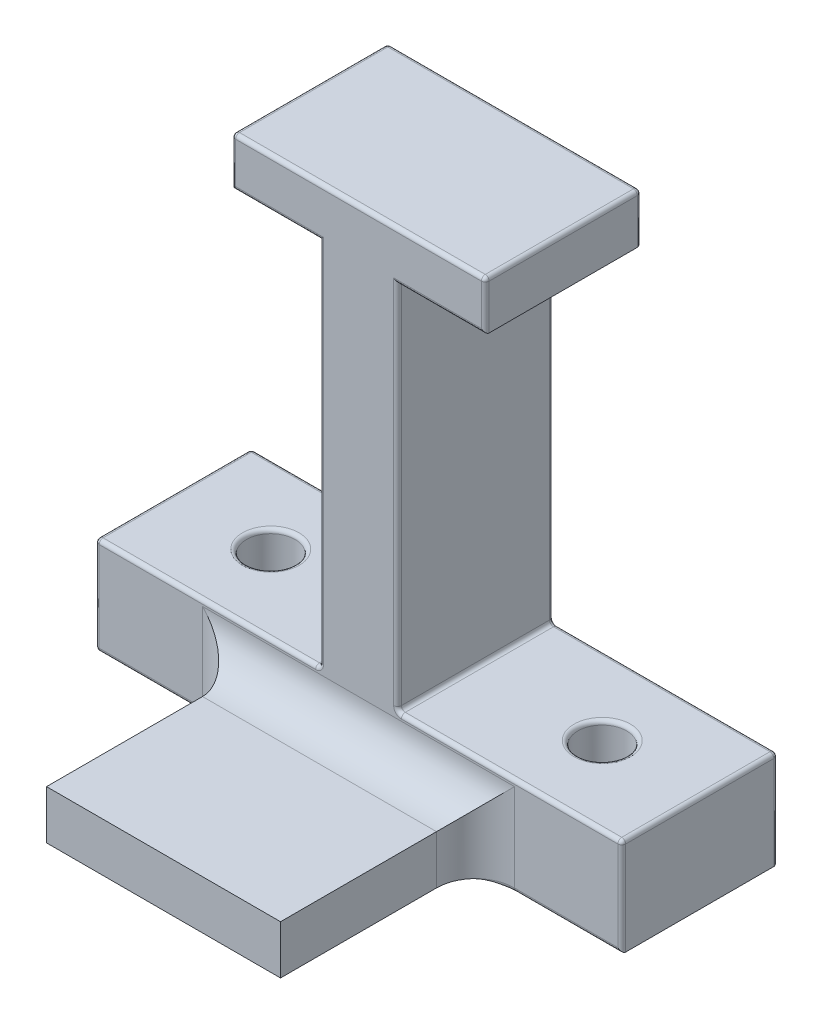
SolidWorks part; units mm, degrees
ref_plane "Front Plane" through (0, 0, 0) normal (0, 0, 1) x (1, 0, 0)
ref_plane "Top Plane" through (0, 0, 0) normal (0, 1, 0) x (1, 0, 0)
ref_plane "Right Plane" through (0, 0, 0) normal (1, 0, 0) x (0, 0, -1)
sketch "Sketch10" plane through (0, 0, 0) normal (0, 0, 1) x (1, 0, 0)
  line L0 (-7.5, 2) -> (-3, 2)
  line L1 (-7.5, 2) -> (-7.5, 4.5)
  line L3 (-7.5, 4.5) -> (5.5, 4.5)
  line L5 (5.5, 4.5) -> (5.5, 2)
  line L6 (5.5, 2) -> (1, 2)
  line L7 (1, 2) -> (1, -17)
  line L9 (1, -17) -> (12.5, -17)
  line L10 (12.5, -17) -> (12.5, -22)
  line L11 (12.5, -22) -> (-14.5, -22)
  line L12 (-14.5, -22) -> (-14.5, -17)
  line L15 (-3, 2) -> (-3, -17)
  line L16 (-3, -17) -> (-14.5, -17)
  dimension "D1" = 4
  dimension "D2" = 13
  dimension "D3" = 4.5
  dimension "D4" = 4.5
  dimension "D5" = 19
  dimension "D6" = 19
  dimension "D7" = 2.5
extrude "Boss-Extrude5" add sketch "Sketch10" along normal blind 8
sketch "Sketch11" plane through (0, -17, 0) normal (0, 1, 0) x (1, 0, 0)
  line L0 (-14.5, -4) -> (-9.5, -4)
  line L1 (-14.5, -8) -> (-14.5, 0) construction
  line L2 (12.5, -4) -> (7.5, -4)
  line L3 (12.5, -8) -> (12.5, 0) construction
  circle A0 centre (-9.5, -4) radius 1.25
  circle A1 centre (7.5, -4) radius 1.25
  dimension "D3" = 2.5
  dimension "D4" = 2.5
  dimension "D1" = 5
  dimension "D2" = 5
extrude "Cut-Extrude5" cut sketch "Sketch11" against normal blind 8 contours A0 | A1 region at (-9.5, -17, 5.2146) region at (6.2854, -17, 4)
fillet "Fillet1" radius 0.2 33 edges at (-1, -22, 0) (12.5, -19.5, 0) (1, -7.5, 0) (3.25, 2, 0) (5.5, 3.25, 0) (-7.5, 3.25, 0) (-5.25, 2, 0) (-3, -7.5, 0) (-14.5, -22, 4) (-14.5, -19.5, 0) (-5.25, 2, 8) (-7.5, 3.25, 8) (5.5, 3.25, 8) (3.25, 2, 8) (1, -7.5, 8) (12.5, -19.5, 8) (-1, -22, 8) (-14.5, -19.5, 8) (-3, -7.5, 8) (12.5, -17, 4) (6.75, -17, 8) (1, -17, 4) (6.75, -17, 0) (7.5, -17, 5.25) (-3, -17, 4) (-8.75, -17, 8) (-14.5, -17, 4) (-8.75, -17, 0) (-9.5, -17, 5.25) (5.5, 4.5, 4) (-1, 4.5, 8) (-7.5, 4.5, 4) (-1, 4.5, 0)
sketch "Sketch12" plane through (0, 0, 8) normal (0, 0, 1) x (1, 0, 0)
  line L0 (-7, -21.8) -> (5, -21.8)
  line L1 (-14.3, -21.8) -> (12.3, -21.8) construction
  line L2 (-7, -21.8) -> (-7, -19.3)
  line L3 (-7, -19.3) -> (5, -19.3)
  line L4 (5, -19.3) -> (5, -21.8)
  point P5 (-1, -21.8)
  dimension "D1" = 12
  dimension "D2" = 2.5
  dimension "D3" = 2.5
extrude "Boss-Extrude6" add sketch "Sketch12" along normal blind 10
fillet "Fillet2" radius 2 4 edges at (5, -20.55, 8) (-1, -19.3, 8) (-7, -20.55, 8) (-1, -21.8, 8)
equation "\"5nn\"=4.94691"
